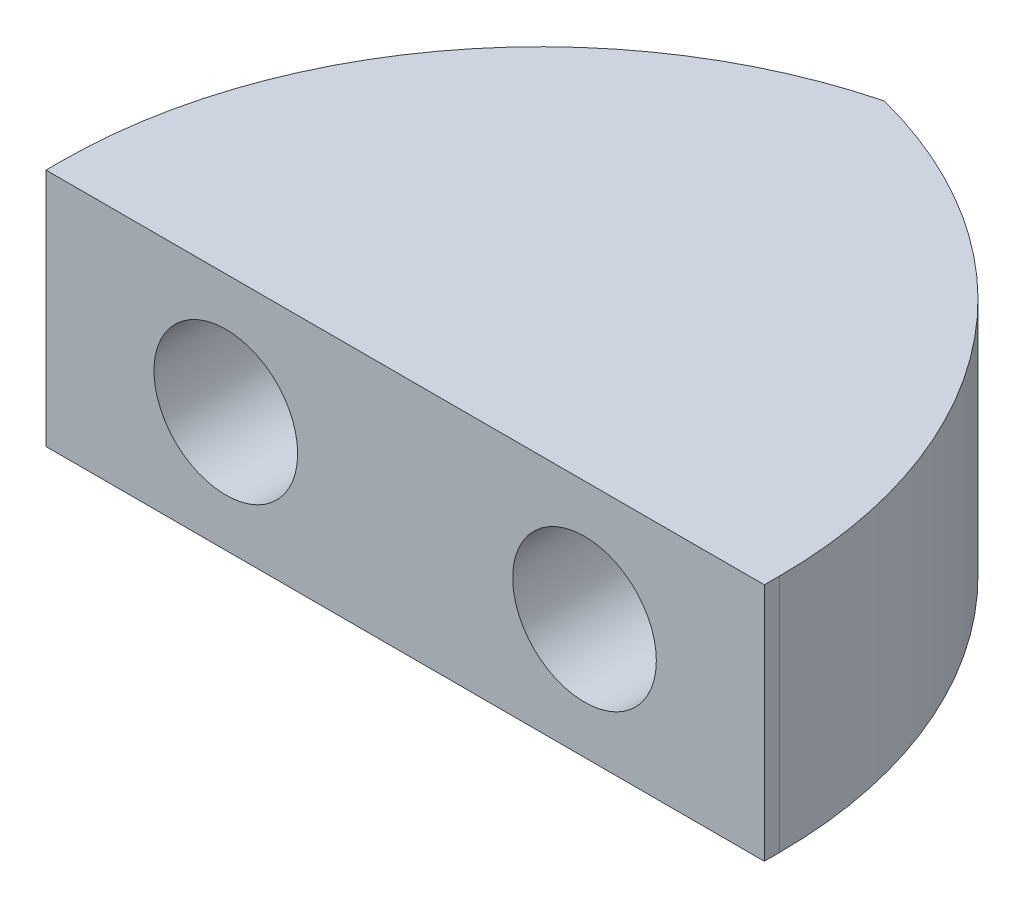
SolidWorks part; units mm, degrees
ref_plane "Front Plane" through (0, 0, 0) normal (0, 0, 1) x (1, 0, 0)
ref_plane "Top Plane" through (0, 0, 0) normal (0, 1, 0) x (1, 0, 0)
ref_plane "Right Plane" through (0, 0, 0) normal (1, 0, 0) x (0, 0, -1)
sketch "Sketch1" plane through (0, 0, 0) normal (0, 0, 1) x (1, 0, 0)
  line L1 (-15, 5) -> (15, 5)
  line L2 (-15, 5) -> (-15, -5)
  line L3 (-15, -5) -> (15, -5)
  line L4 (15, 5) -> (15, -5)
  line L5 (-15, 5) -> (15, -5) construction
  line L6 (-15, -5) -> (15, 5) construction
  point P0 (0, 0)
  dimension "D1" = 30
  dimension "D2" = 10
extrude "Boss-Extrude1" add sketch "Sketch1" along normal blind 20.64
hole_wizard "M3 Clearance Hole1" positions "Sketch4" profile "Sketch5" hole size "M3" standard "ANSI Metric" end condition through all
sketch "Sketch4" plane through (0, 0, 20.64) normal (0, 0, 1) x (1, 0, 0)
  line L0 (-15, 0) -> (15, 0) construction
  line L1 (-15, 5) -> (-15, -5) construction
  line L2 (15, -5) -> (15, 5) construction
  point P0 (7.5, 0)
  point P3 (-7.5, 0)
  dimension "D1" = 0
  dimension "D2" = 0
  dimension "D3" = 7.5
  dimension "D4" = 7.5
sketch "Sketch5" plane through (7.5, 0, 20.64) normal (1, 0, 0) x (0, -1, 0)
  line L0 (0, 0) -> (0, 20.64)
  line L1 (0, 20.64) -> (1.7, 20.64)
  line L2 (1.7, 20.64) -> (1.7, 0)
  line L5 (1.7, 0) -> (0, 0)
  line L11 (0, -6.35) -> (0, 107.95) construction
  dimension "Thru Hole Dia." = 3.4
  dimension "Thru Hole Depth" = 20.64
fillet "Fillet1" radius 20 2 edges at (15, 0, 0) (-15, 0, 0)
sketch "Sketch7" plane through (0, 0, 20.64) normal (0, 0, 1) x (1, 0, 0)
  line L0 (-14.9898, 0) -> (14.9898, 0) construction
  line L1 (-14.9898, 5) -> (-14.9898, -5) construction
  line L2 (14.9898, -5) -> (14.9898, 5) construction
  circle A0 centre (-7.4898, 0) radius 3
  circle A1 centre (7.4898, 0) radius 3
  dimension "D2" = 6
  dimension "D4" = 6
  dimension "D1" = 7.5
  dimension "D3" = 7.5
extrude "Cut-Extrude1" cut sketch "Sketch7" against normal blind 11
